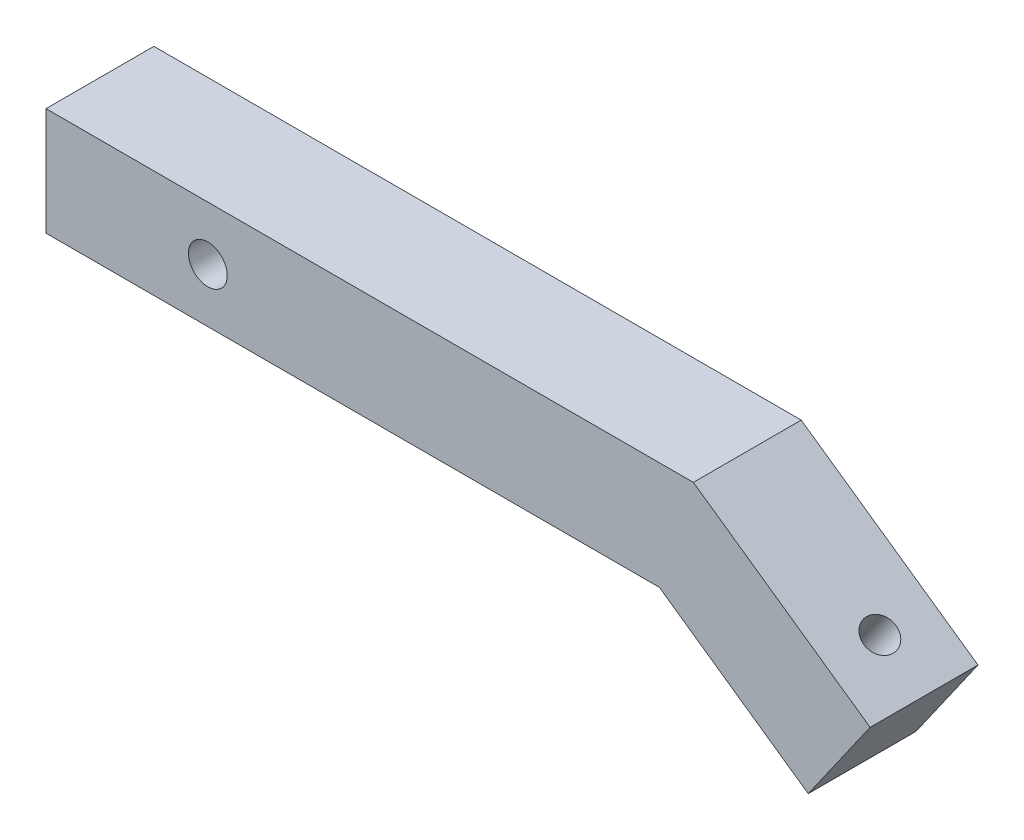
SolidWorks part; units mm, degrees
ref_plane "Front Plane" through (0, 0, 0) normal (0, 0, 1) x (1, 0, 0)
ref_plane "Top Plane" through (0, 0, 0) normal (0, 1, 0) x (1, 0, 0)
ref_plane "Right Plane" through (0, 0, 0) normal (1, 0, 0) x (0, 0, -1)
sketch "Sketch1" plane through (0, 0, 0) normal (0, 0, 1) x (1, 0, 0)
  line L0 (0, 0) -> (76.2, 0)
  line L1 (76.2, 0) -> (97.0065, -14.5688)
  line L2 (97.0065, -14.5688) -> (89.722, -24.9721)
  line L3 (89.722, -24.9721) -> (72.1957, -12.7)
  line L4 (72.1957, -12.7) -> (0, -12.7)
  line L5 (0, -12.7) -> (0, 0)
  dimension "D1" = 12.7
  dimension "D2" = 12.7
  dimension "D3" = 145
  dimension "D4" = 76.2
  dimension "D5" = 25.4
extrude "Boss-Extrude1" add sketch "Sketch1" along normal blind 12.7
sketch "Sketch2" plane through (0, 0, 0) normal (0, 0, -1) x (-1, 0, 0)
  line L0 (0, 0) -> (0, -12.7) construction
  line L1 (0, -12.7) -> (-72.1957, -12.7) construction
  circle A0 centre (-19.05, -6.35) radius 2.286
  dimension "D1" = 4.572
  dimension "D3" = 6.35
  dimension "D2" = 19.05
extrude "Cut-Extrude1" cut sketch "Sketch2" against normal blind 12.7
sketch "Sketch3" plane through (17.7846, 25.3991, 0) normal (-0.5736, -0.8192, 0) x (0.8192, -0.5736, 0)
  line L0 (66.4237, 0) -> (87.8194, 0) construction
  line L1 (87.8194, 12.7) -> (87.8194, 0) construction
  circle A0 centre (81.4694, 6.35) radius 1.905
  dimension "D3" = 3.81
  dimension "D1" = 6.35
  dimension "D2" = 6.35
extrude "Cut-Extrude2" cut sketch "Sketch3" against normal blind 12.7
